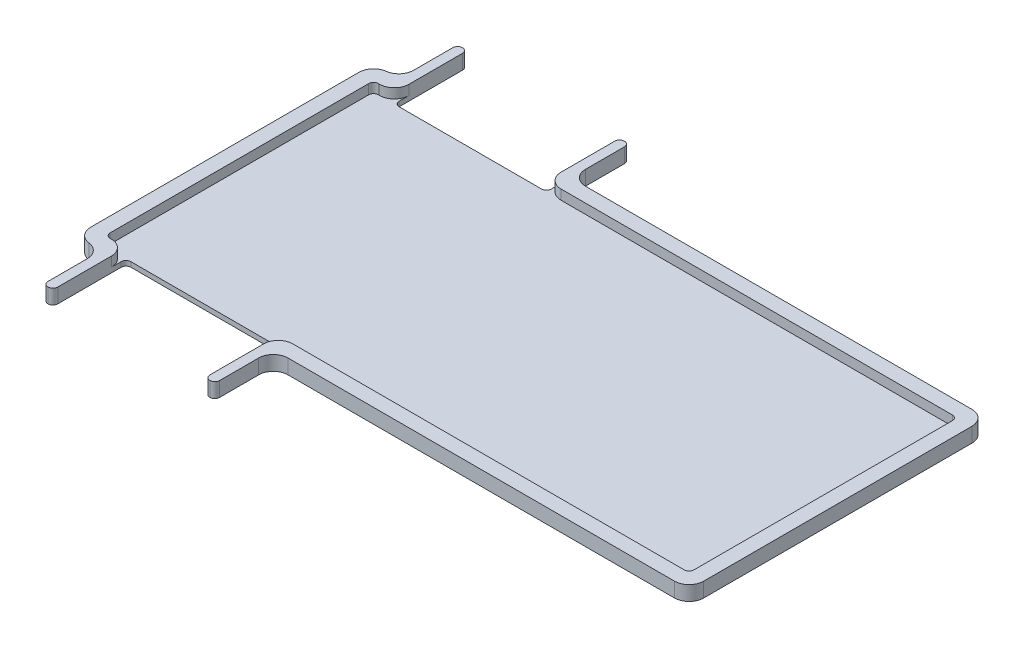
SolidWorks part; units mm, degrees
ref_plane "Front Plane" through (0, 0, 0) normal (0, 0, 1) x (1, 0, 0)
ref_plane "Top Plane" through (0, 0, 0) normal (0, 1, 0) x (1, 0, 0)
ref_plane "Right Plane" through (0, 0, 0) normal (1, 0, 0) x (0, 0, -1)
sketch "Sketch3" plane through (0, 0, 0) normal (0, 1, 0) x (1, 0, 0)
  line L0 (0, -27.5) -> (0, 27.5) construction
  line L1 (-59.85, -27.5) -> (59.85, -27.5)
  line L2 (-59.85, -27.5) -> (-59.85, 27.5)
  line L3 (-59.85, 27.5) -> (59.85, 27.5)
  line L4 (59.85, -27.5) -> (59.85, 27.5)
  line L5 (-59.85, -27.5) -> (59.85, 27.5) construction
  line L6 (-59.85, 27.5) -> (59.85, -27.5) construction
  line L7 (-59.85, 0) -> (59.85, 0) construction
  line L8 (-40, -27.5) -> (-40, 27.5) construction
  line L9 (-62.85, 30.5) -> (-57.6, 30.5)
  line L10 (62.85, -30.5) -> (62.85, 30.5)
  line L11 (-62.85, -30.5) -> (-57.6, -30.5)
  line L12 (-62.85, -30.5) -> (-62.85, 30.5)
  line L13 (-57.6, 30.5) -> (-57.6, 42.5)
  line L14 (-57.6, 42.5) -> (-55.6, 42.5)
  line L15 (-55.6, 42.5) -> (-55.6, 27.5)
  line L16 (-22.4, 42.5) -> (-24.4, 42.5)
  line L17 (-22.4, 30.5) -> (-22.4, 42.5)
  line L18 (-24.4, 42.5) -> (-24.4, 27.5)
  line L19 (-55.6, 27.5) -> (-59.85, 27.5)
  line L20 (-62.85, 30.5) -> (62.85, 30.5) construction
  line L21 (-22.4, 30.5) -> (62.85, 30.5)
  line L22 (-59.85, -27.5) -> (59.85, -27.5)
  line L23 (59.85, 27.5) -> (-24.4, 27.5)
  line L24 (-22.4, -30.5) -> (-22.4, -42.5)
  line L25 (-24.4, -42.5) -> (-24.4, -27.5)
  line L26 (-22.4, -42.5) -> (-24.4, -42.5)
  line L27 (-57.6, -42.5) -> (-55.6, -42.5)
  line L28 (-55.6, -42.5) -> (-55.6, -27.5)
  line L29 (-57.6, -30.5) -> (-57.6, -42.5)
  line L30 (-22.4, -30.5) -> (62.85, -30.5)
  line L31 (-62.85, -30.5) -> (62.85, -30.5) construction
  point P0 (0, 0)
  point P9 (0, 0)
  point P12 (0, 0)
  point P15 (-40, 0)
  dimension "D1" = 119.7
  dimension "D2" = 55
  dimension "D3" = 40
  dimension "D5" = 15.6
  dimension "D6" = 2
  dimension "D7" = 12
  dimension "D8" = 12
  dimension "D4" = 3
extrude "Boss-Extrude6" add sketch "Sketch3" along normal blind 3 contours L11 L29 L27 L28 L1 L2 L3 L15 L14 L13 L9 L12 | L24 L30 L10 L21 L17 L16 L18 L3 L4 L22 L25 L26 region at (-60.1007, 0, 0) region at (17.725, 0, 28.7181)
sketch "Sketch4" plane through (0, 0, 0) normal (0, 1, 0) x (1, 0, 0)
  line L1 (-59.85, 27.5) -> (59.85, 27.5)
  line L2 (-59.85, 27.5) -> (-59.85, -27.5)
  line L3 (-59.85, -27.5) -> (59.85, -27.5)
  line L4 (59.85, 27.5) -> (59.85, -27.5)
extrude "Boss-Extrude7" add sketch "Sketch4" along normal blind 1
fillet "Fillet13" radius 3 4 edges at (62.85, 1.5, -30.5) (62.85, 1.5, 30.5) (-62.85, 1.5, 30.5) (-62.85, 1.5, -30.5)
fillet "Fillet14" radius 1 4 edges at (59.85, 2, 27.5) (59.85, 2, -27.5) (-59.85, 2, -27.5) (-59.85, 2, 27.5)
fillet "Fillet15" radius 1 8 edges at (-22.4, 1.5, 42.5) (-24.4, 1.5, 42.5) (-55.6, 1.5, 42.5) (-57.6, 1.5, 42.5) (-55.6, 1.5, -42.5) (-57.6, 1.5, -42.5) (-22.4, 1.5, -42.5) (-24.4, 1.5, -42.5)
fillet "Fillet16" radius 3 4 edges at (-22.4, 1.5, -30.5) (-57.6, 1.5, -30.5) (-57.6, 1.5, 30.5) (-22.4, 1.5, 30.5)
fillet "Fillet17" radius 3 2 edges at (-55.6, 2, -27.5) (-24.4, 2, -27.5)
fillet "Fillet18" radius 1 2 edges at (-55.6, 0.5, -27.5) (-24.4, 0.5, -27.5)
fillet "Fillet19" radius 3 2 edges at (-55.6, 2, 27.5) (-24.4, 2, 27.5)
fillet "Fillet20" radius 1 2 edges at (-24.4, 0.5, 27.5) (-55.6, 0.5, 27.5)
